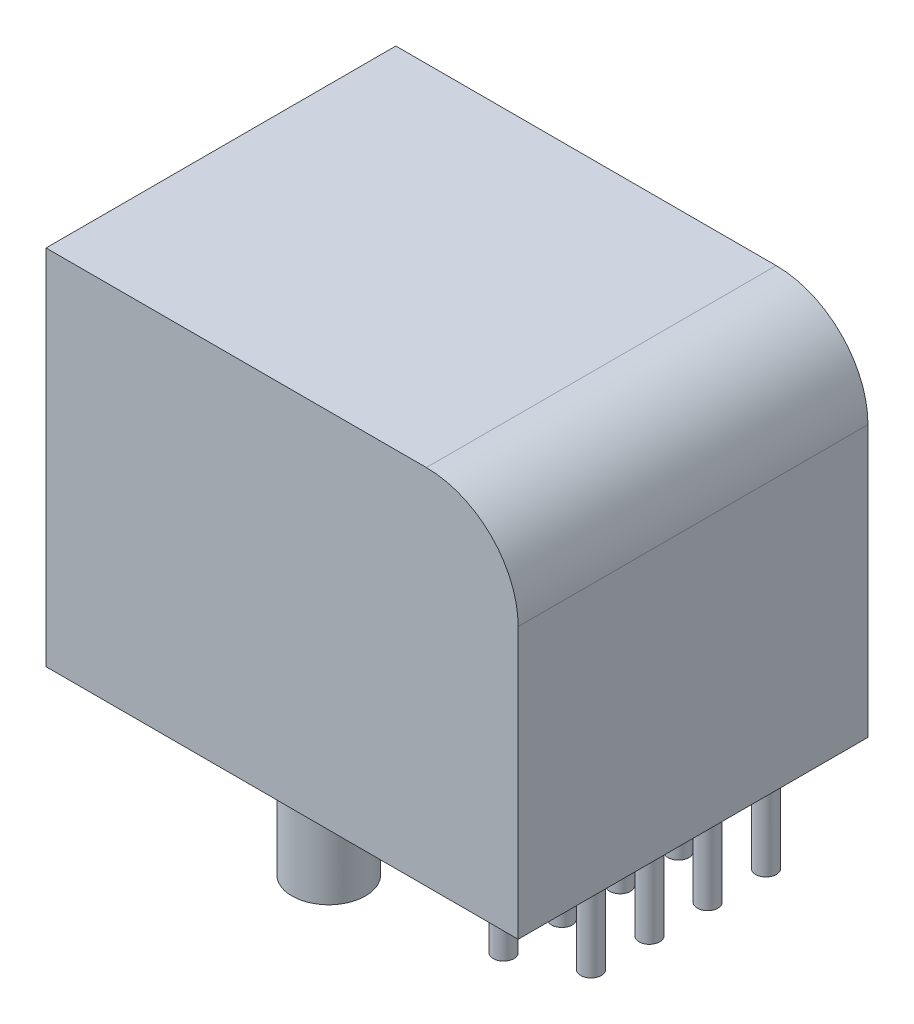
SolidWorks part; units mm, degrees
ref_plane "Front Plane" through (0, 0, 0) normal (0, 0, 1) x (1, 0, 0)
ref_plane "Top Plane" through (0, 0, 0) normal (0, 1, 0) x (1, 0, 0)
ref_plane "Right Plane" through (0, 0, 0) normal (1, 0, 0) x (0, 0, -1)
sketch "Sketch1" plane through (0, 0, 0) normal (0, 0, 1) x (1, 0, 0)
  line L1 (-10.285, -7.9) -> (10.285, -7.9)
  line L2 (-10.285, -7.9) -> (-10.285, 7.9)
  line L3 (-10.285, 7.9) -> (10.285, 7.9)
  line L4 (10.285, -7.9) -> (10.285, 7.9)
  line L5 (-10.285, -7.9) -> (10.285, 7.9) construction
  line L6 (-10.285, 7.9) -> (10.285, -7.9) construction
  point P0 (0, 0)
  dimension "D1" = 20.57
  dimension "D2" = 15.8
extrude "Boss-Extrude1" add sketch "Sketch1" along normal blind 15.24 contours L3 L4 L1 L2
fillet "Fillet1" radius 4 1 edges at (10.285, 7.9, 7.62)
sketch "Sketch2" plane through (0, -7.9, 0) normal (0, -1, 0) x (1, 0, 0)
  line L0 (-10.285, 7.62) -> (10.285, 7.62) construction
  line L1 (-10.285, 15.24) -> (-10.285, 0) construction
  line L2 (10.285, 15.24) -> (10.285, 0) construction
  line L3 (0.125, 1.905) -> (0.125, 13.335) construction
  line L4 (9.015, 13.0064) -> (9.015, 2.2336) construction
  line L5 (6.475, 2.2336) -> (6.475, 13.0064) construction
  circle A0 centre (0.125, 13.335) radius 1.6
  circle A1 centre (0.125, 1.905) radius 1.6
  circle A2 centre (9.015, 8.255) radius 0.45
  circle A3 centre (6.475, 6.985) radius 0.45
  point P11 (0.125, 7.62)
  point P15 (9.015, 7.62)
  point P16 (6.475, 7.62)
  dimension "D1" = 3.2
  dimension "D6" = 0.9
  dimension "D2" = 11.43
  dimension "D3" = 10.41
  dimension "D4" = 8.89
  dimension "D5" = 2.54
  dimension "D7" = 0.635
  dimension "D8" = 1.27
extrude "Boss-Extrude2" add sketch "Sketch2" along normal blind 3.6 contours A1 | A0 region at (0.125, -7.9, 1.905)
extrude "Boss-Extrude3" add sketch "Sketch2<4>" along normal blind 4 contours A3 region at (6.475, -7.9, 6.985)
sketch "Sketch2<4>" plane through (0, -7.9, 0) normal (0, -1, 0) x (1, 0, 0) same geometry as "Sketch2"
extrude "Boss-Extrude4" add sketch "Sketch2<5>" along normal blind 4 contours A2
sketch "Sketch2<5>" plane through (0, -7.9, 0) normal (0, -1, 0) x (1, 0, 0) same geometry as "Sketch2"
pattern_linear "LPattern1" count 3 spacing 2.54 along (0, 0, -1) count 2 spacing 2.54 along (0, 0, 1) of "Boss-Extrude4"
pattern_linear "LPattern2" count 2 spacing 2.54 along (0, 0, -1) count 3 spacing 2.54 along (0, 0, 1) of "Boss-Extrude3"
